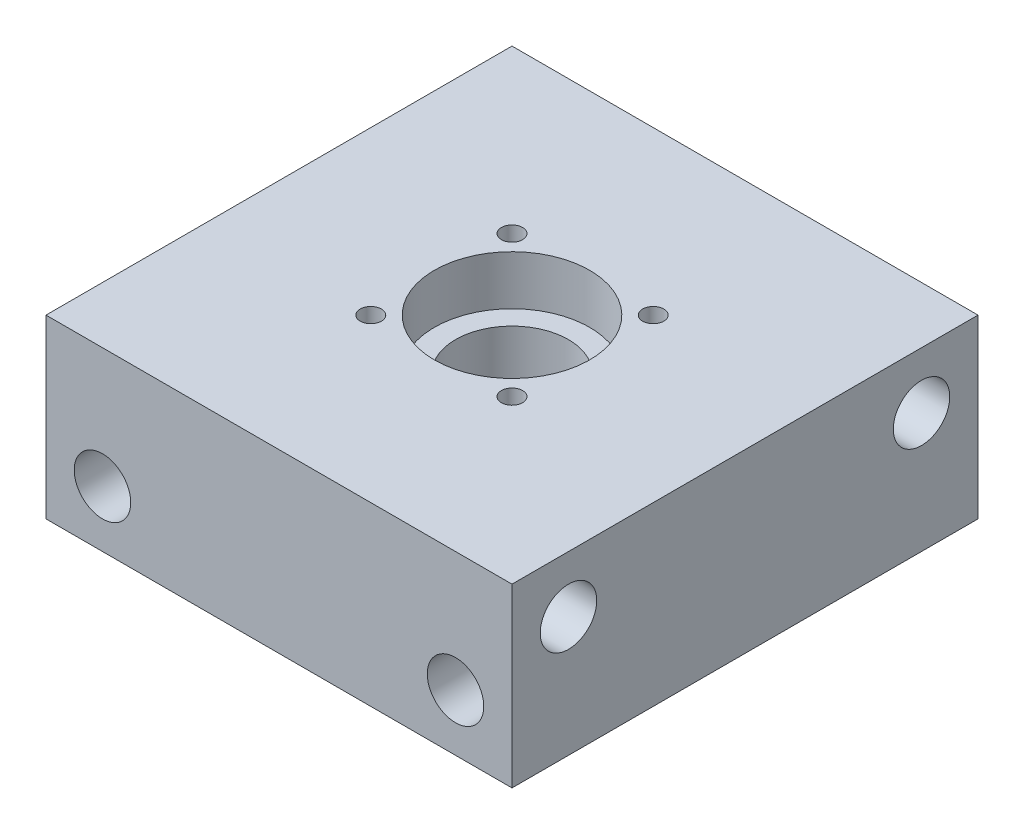
SolidWorks part; units mm, degrees
material "ABS"
ref_plane "Front Plane" through (0, 0, 0) normal (0, 0, 1) x (1, 0, 0)
ref_plane "Top Plane" through (0, 0, 0) normal (0, 1, 0) x (1, 0, 0)
ref_plane "Right Plane" through (0, 0, 0) normal (1, 0, 0) x (0, 0, -1)
sketch "Sketch1" plane through (0, 0, 0) normal (0, 1, 0) x (1, 0, 0)
  line L0 (-25, 94.322) -> (-25, -161.1056) construction
  line L1 (0, 212.1837) -> (0, -209.6879) construction
  line L2 (-178.557, 25) -> (189.3494, 25) construction
  line L3 (-284.8586, 0) -> (271.277, 0) construction
  line L4 (-33, 29) -> (33, 29)
  line L5 (-29, 33) -> (-21, 33)
  line L6 (-29, 33) -> (-29, -33)
  line L7 (-29, -33) -> (-21, -33)
  line L8 (-21, 33) -> (-21, -33)
  line L9 (-33, 21) -> (33, 21)
  line L10 (-33, -29) -> (-33, -21)
  line L11 (-178.557, -25) -> (189.3494, -25) construction
  line L12 (33, -29) -> (33, -21)
  line L13 (-33, 29) -> (33, 29)
  line L14 (-33, 29) -> (-33, 21)
  line L15 (-33, 21) -> (33, 21)
  line L16 (33, 29) -> (33, 21)
  line L17 (-33, -21) -> (33, -21)
  line L18 (-33, -29) -> (33, -29)
  line L19 (-33, -21) -> (33, -21)
  line L20 (-33, -29) -> (33, -29)
  line L21 (29, -33) -> (21, -33)
  line L22 (29, 33) -> (21, 33)
  line L23 (25, 94.322) -> (25, -161.1056) construction
  line L24 (21, 33) -> (21, -33)
  line L25 (29, 33) -> (29, -33)
  line L26 (13.2332, 10) -> (11.6166, 12.8)
  line L27 (-33, 33) -> (33, 33)
  line L28 (-33, 33) -> (-33, -33)
  line L29 (-33, -33) -> (33, -33)
  line L30 (33, 33) -> (33, -33)
  line L31 (-6.7668, 10) -> (-8.3834, 12.8)
  line L32 (-8.3834, 12.8) -> (-11.6166, 12.8)
  line L33 (-11.6166, 12.8) -> (-13.2332, 10)
  line L34 (-13.2332, 10) -> (-11.6166, 7.2)
  line L35 (-11.6166, 7.2) -> (-8.3834, 7.2)
  line L36 (-8.3834, 7.2) -> (-6.7668, 10)
  line L37 (11.6166, 12.8) -> (8.3834, 12.8)
  line L38 (8.3834, 12.8) -> (6.7668, 10)
  line L39 (6.7668, 10) -> (8.3834, 7.2)
  line L40 (8.3834, 7.2) -> (11.6166, 7.2)
  line L41 (11.6166, 7.2) -> (13.2332, 10)
  line L42 (13.2332, -10) -> (11.6166, -7.2)
  line L43 (11.6166, -7.2) -> (8.3834, -7.2)
  line L44 (8.3834, -7.2) -> (6.7668, -10)
  line L45 (6.7668, -10) -> (8.3834, -12.8)
  line L46 (8.3834, -12.8) -> (11.6166, -12.8)
  line L47 (11.6166, -12.8) -> (13.2332, -10)
  line L48 (-6.7668, -10) -> (-8.3834, -7.2)
  line L49 (-8.3834, -7.2) -> (-11.6166, -7.2)
  line L50 (-11.6166, -7.2) -> (-13.2332, -10)
  line L51 (-13.2332, -10) -> (-11.6166, -12.8)
  line L52 (-11.6166, -12.8) -> (-8.3834, -12.8)
  line L53 (-8.3834, -12.8) -> (-6.7668, -10)
  circle A0 centre (0, 0) radius 11
  circle A1 centre (0, 0) radius 8
  circle A2 centre (-10, 10) radius 1.5
  circle A3 centre (10, 10) radius 1.5
  circle A4 centre (10, 10) radius 2.8 construction
  circle A5 centre (10, -10) radius 1.5
  circle A6 centre (-10, 10) radius 2.8 construction
  circle A7 centre (10, -10) radius 2.8 construction
  circle A8 centre (-10, -10) radius 1.5
  circle A9 centre (-10, -10) radius 2.8 construction
  dimension "D5" = 2
  dimension "D6" = 2
  dimension "D7" = 3
  dimension "D14" = 5.6
  dimension "D2" = 25
  dimension "D3" = 25
  dimension "D4" = 4
  dimension "D8" = 10
  dimension "D9" = 10
  dimension "D12" = 8
  dimension "D13" = 4
extrude "Boss-Extrude1" add sketch "Sketch1" along normal blind 25 contours L24 L9 L8 L17 A3 A2 A0 | L24 L4 L8 L9 | L6 L9 L8 L4 | L27 L8 L4 L24 | L8 L5 L6 L4 | L27 L28 L4 L6 | L4 L14 L9 L6 | L9 L28 L17 L6 | L6 L17 L8 L9 | L6 L18 L8 L17 | L10 L18 L6 L17 | L28 L29 L6 L18 | L18 L6 L7 L8 | L24 L17 L8 L18 | L8 L29 L24 L18 | L25 L20 L24 L21 | L25 L19 L24 L20 | L17 L25 L18 L12 | L30 L18 L25 L29 | L25 L15 L24 L19 | L30 L9 L25 L17 | L25 L13 L24 L15 | L4 L25 L9 L16 | L25 L22 L24 L13 | L30 L27 L25 L4 | L35 L36 L31 L32 L33 L34 A2 | L40 L41 L26 L37 L38 L39 A3 | L46 L47 L42 L43 L44 L45 A5 | L52 L53 L48 L49 L50 L51 A8 region at (-31, 0, -31) region at (-31, 0, -25) region at (-25, 0, -31) region at (-25, 0, -25) region at (-31, 0, 0) region at (0, 0, -31) region at (0, 0, -25) region at (-25, 0, 0) region at (-31, 0, 25) region at (25, 0, -31) region at (25, 0, -25) region at (0, 0, -20.406) region at (-25, 0, 25) region at (-31, 0, 31) region at (31, 0, -31) region at (31, 0, -25) region at (25, 0, 0) region at (0, 0, 25) region at (-25, 0, 31) region at (31, 0, 0) region at (25, 0, 25) region at (0, 0, 31) region at (31, 0, 25) region at (25, 0, 31) region at (31, 0, 31) region at (12.3508, 0, -8.6428) region at (-7.6492, 0, -8.6428) region at (12.3508, 0, 11.3572) region at (-7.6492, 0, 11.3572)
extrude "Boss-Extrude2" add sketch "Sketch1<4>" along normal blind 18 contours A0 A1 region at (-10.6889, 0, 0)
sketch "Sketch1<4>" plane through (0, 0, 0) normal (0, 1, 0) x (1, 0, 0) same geometry as "Sketch1"
sketch "Sketch2" plane through (-33, 0, 0) normal (-1, 0, 0) x (0, 0, 1)
  line L0 (0, 0) -> (0, 25) construction
  line L1 (-33, 25) -> (33, 25) construction
  circle A0 centre (-25, 17) radius 4
  circle A1 centre (25, 17) radius 4
  dimension "D3" = 8
  dimension "D1" = 25
  dimension "D2" = 8
extrude "Cut-Extrude1" cut sketch "Sketch2" against normal through all
sketch "Sketch3" plane through (0, 0, -33) normal (0, 0, -1) x (-1, 0, 0)
  line L0 (0, 0) -> (0, 25) construction
  line L1 (33, 25) -> (-33, 25) construction
  line L2 (33, 0) -> (-33, 0) construction
  circle A0 centre (-25, 8) radius 4
  circle A1 centre (25, 8) radius 4
  dimension "D1" = 8
  dimension "D2" = 25
  dimension "D3" = 8
extrude "Cut-Extrude2" cut sketch "Sketch3" against normal through all
extrude "Cut-Extrude3" cut sketch "Sketch1<5>" along normal blind 16.833 contours L52 L53 L48 L49 L50 L51 A8 | L35 L36 L31 L32 L33 L34 A2 | L40 L41 L26 L37 L38 L39 A3 | L46 L47 L42 L43 L44 L45 A5 region at (12.3508, 0, -8.6428) region at (-7.6492, 0, -8.6428) region at (12.3508, 0, 11.3572) region at (-7.6492, 0, 11.3572)
sketch "Sketch1<5>" plane through (0, 0, 0) normal (0, 1, 0) x (1, 0, 0) same geometry as "Sketch1"
equation "\"rod_diameter\"= 8"
equation "\"rod_hole_thickness\"= 4"
equation "\"rod_radius\"= \"rod_diameter\" / 2"
equation "\"platter_diameter\"= 320"
equation "\"platter_radius\"= \"platter_diameter\" / 2"
equation "\"extruder_mount_hole_spacing\"= 75"
equation "\"arm_rod_spacing\"= 40"
equation "\"top_frame_rod_spacing\"= \"arm_rod_spacing\" + 40"
equation "\"motor_level_rod_spacing\"= 15"
equation "\"linear_bearing_diameter\"= 15"
equation "\"z_rod_spacing\"= 75"
equation "\"platter_rod_spacing\"= 50"
equation "\"rod_nut_thickness\"= 6.5"
equation "\"rod_nut_inscribed_diameter\"= 13"
equation "\"D2@Sketch1\"=\"platter_rod_spacing\"/2"
equation "\"D3@Sketch1\"=\"platter_rod_spacing\"/2"
equation "\"D12@Sketch1\"=\"rod_diameter\""
equation "\"D4@Sketch1\"=\"rod_hole_thickness\""
equation "\"D13@Sketch1\"=\"rod_hole_thickness\""
equation "\"D1@Boss-Extrude1\"= \"rod_diameter\" * 2 + \"rod_hole_thickness\" * 2 + 1"
equation "\"D1@Boss-Extrude2\"= \"D1@Boss-Extrude1\" - 7"
equation "\"D1@Sketch2\"=\"platter_rod_spacing\"/2"
equation "\"D2@Sketch2\"=\"rod_radius\"+\"rod_hole_thickness\""
equation "\"D3@Sketch2\"=\"rod_diameter\""
equation "\"D1@Sketch3\"=\"rod_diameter\""
equation "\"D2@Sketch3\"=\"platter_rod_spacing\"/2"
equation "\"D3@Sketch3\"=\"rod_radius\"+\"rod_hole_thickness\""
equation "\"top_frame_spacing\"= 90"
equation "\"z_drive_rod_offset\"= 12"
equation "\"z_height\"= 400"
equation "\"gear_pitch\"=2"
equation "\"r_gear_teeth\"= 450"
equation "\"theta_gear_teeth\"= 385"
equation "\"sheet_thickness\"=5.333"
equation "\"sheet_tab_hole_thickness\"= \"sheet_thickness\""
equation "\"sheet_tab_width\"= \"sheet_thickness\"*2"
equation "\"sheet_double_tab_width\"= 35"
equation "\"sheet_bolt_diameter\"= 3"
equation "\"sheet_bolt_length\"= 16"
equation "\"sheet_nut_diameter\"= 5.5"
equation "\"sheet_nut_thickness\"= 2.5"
equation "\"sheet_nut_depth\"= 10"
equation "\"bearing_outside_diameter\"= 22"
equation "\"bearing_thickness\"= 7"
equation "\"corner_part_thickness\"= \"sheet_thickness\" + \"bearing_thickness\""
equation "\"setscrew_nut_diameter\"= 6"
equation "\"setscrew_nut_thickness\"= 3"
equation "\"setscrew_bolt_diameter\"= 3"
equation "\"motor_shaft_diameter\"= 5.7"
equation "\"D1@Cut-Extrude3\"= \"D1@Boss-Extrude1\" - \"sheet_bolt_length\" + \"sheet_nut_thickness\" + \"sheet_thickness\""
